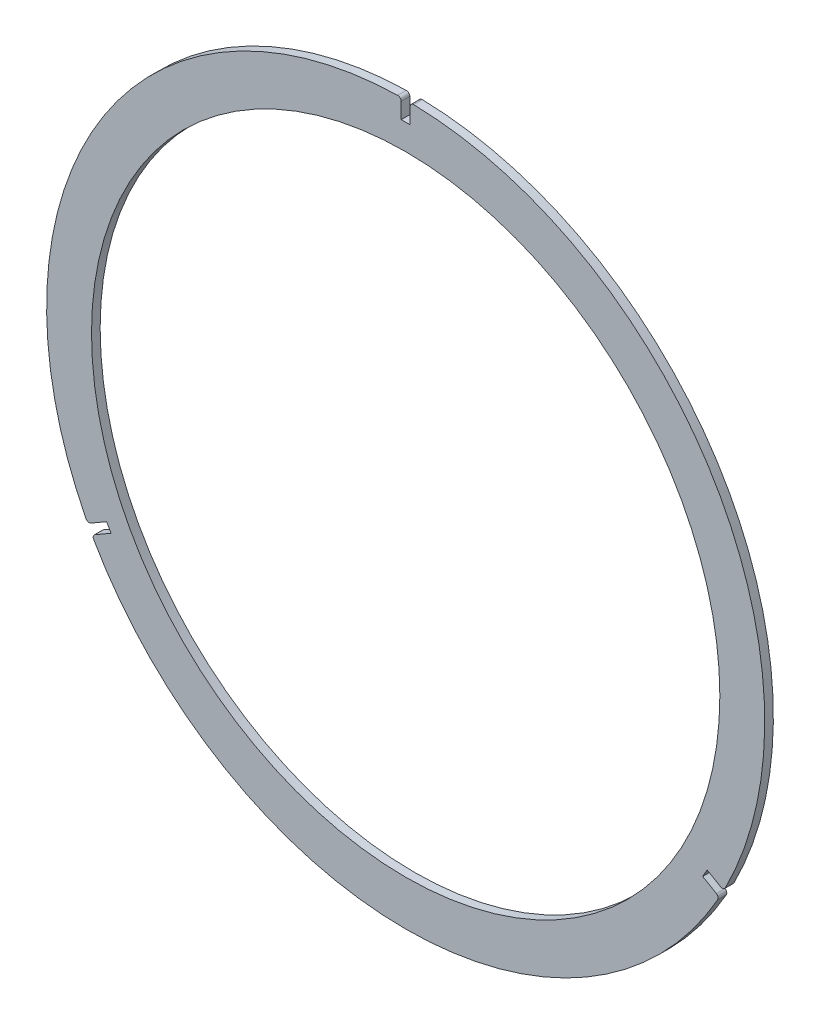
SolidWorks part; units mm, degrees
material "Balsa"
ref_plane "Front Plane" through (0, 0, 0) normal (0, 0, 1) x (1, 0, 0)
ref_plane "Top Plane" through (0, 0, 0) normal (0, 1, 0) x (1, 0, 0)
ref_plane "Right Plane" through (0, 0, 0) normal (1, 0, 0) x (0, 0, -1)
sketch "Sketch2" plane through (0, 0, 0) normal (0, 0, 1) x (1, 0, 0)
  line L0 (0, 0) -> (0, 236.6718) construction
  line L1 (-1.651, 128.5137) -> (-1.651, 121.4017)
  line L3 (1.651, 128.5137) -> (1.651, 121.4017)
  line L4 (-1.651, 121.4017) -> (1.651, 121.4017)
  line L5 (-136.2076, -77.8947) -> (0.0002, 0.7357) construction
  line L6 (-136.2076, -77.8947) -> (0.0002, 0.7357) construction
  line L7 (136.2041, -77.9016) -> (0.0002, 0.7357) construction
  line L8 (136.2041, -77.9016) -> (0.0002, 0.7357) construction
  line L9 (-116.9771, -64.8869) -> (-110.0184, -60.8698)
  line L10 (-115.4068, -67.7931) -> (-108.3675, -63.7295)
  line L11 (-110.0184, -60.8698) -> (-108.3675, -63.7295)
  line L12 (-117.5533, -65.2196) -> (-116.9771, -64.8869) construction
  line L13 (-115.9024, -68.0792) -> (-115.4068, -67.7931) construction
  line L14 (115.4068, -67.7931) -> (109.2475, -64.2371)
  line L15 (110.8985, -61.3775) -> (109.2475, -64.2371)
  line L16 (116.9771, -64.8869) -> (110.8985, -61.3775)
  arc A0 (-1.651, 128.5137) -> (-116.9771, -64.8869) centre (0, -3.556) ccw
  arc A1 (0.0665, 128.1531) -> (63.0696, -118.8475) centre (0, -3.3993) ccw construction
  circle A2 centre (0, -3.556) radius 115.57
  arc A3 (63.0696, -118.8475) -> (0.0665, 128.1531) centre (0, -3.3993) ccw construction
  arc A4 (0, 128.524) -> (-1.651, 128.5137) centre (0, -3.556) ccw construction
  circle A5 centre (0, -3.556) radius 132.08 construction
  arc A6 (1.651, 128.5137) -> (0, 128.524) centre (0, -3.556) ccw construction
  arc A7 (-116.9771, -64.8869) -> (-116.2009, -66.3452) centre (0, -3.556) ccw construction
  arc A8 (-115.4068, -67.7931) -> (115.4068, -67.7931) centre (0, -3.556) ccw
  arc A9 (-116.2009, -66.3452) -> (-115.4068, -67.7931) centre (0, -3.556) ccw construction
  arc A10 (115.4068, -67.7931) -> (116.1978, -66.3509) centre (0, -3.556) ccw construction
  arc A11 (116.9771, -64.8869) -> (1.651, 128.5137) centre (0, -3.556) ccw
  arc A12 (116.1978, -66.3509) -> (116.9771, -64.8869) centre (0, -3.556) ccw construction
  point P24 (-115.4068, -67.7931)
  dimension "D1" = 3.556
  dimension "D3" = 264.16
  dimension "D2" = 16.51
  dimension "D4" = 3.302
  dimension "D5" = 7.112
  dimension "D6" = 3.302
  dimension "D7" = 8.128
  dimension "D8" = 7.076
extrude "Boss-Extrude1" add sketch "Sketch2" along normal mid plane 3.175
fillet "Fillet1" radius 1.27 6 edges at (116.9771, -64.8869, 0) (115.4068, -67.7931, 0) (1.651, 128.5137, 0) (-1.651, 128.5137, 0) (-115.4068, -67.7931, 0) (-116.9771, -64.8869, 0)
